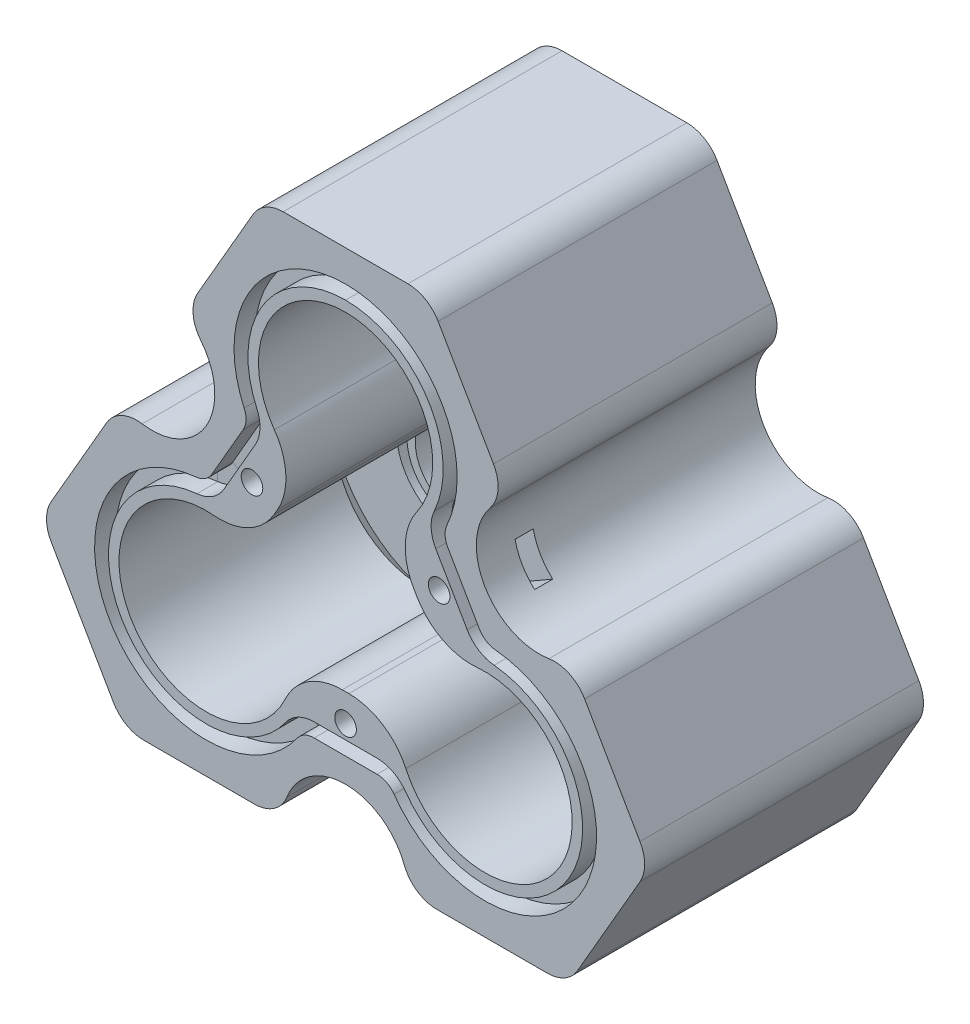
SolidWorks part; units mm, degrees
ref_plane "前视基准面" through (0, 0, 0) normal (0, 0, 1) x (1, 0, 0)
ref_plane "上视基准面" through (0, 0, 0) normal (0, 1, 0) x (1, 0, 0)
ref_plane "右视基准面" through (0, 0, 0) normal (1, 0, 0) x (0, 0, -1)
ref_plane "基准面1" through (0, -12.4, 0) normal (0, 1, 0) x (1, 0, 0)
sketch "草图2" plane through (0, 0, 0) normal (0, 0, 1) x (1, 0, 0)
  line L1 (-9.7628, 6.1843) -> (-10.2372, 5.3627)
  line L2 (-0.4744, -11.547) -> (0.4744, -11.547)
  line L3 (10.2372, 5.3627) -> (9.7628, 6.1843)
  circle A0 centre (0, 0) radius 11.547 construction
  arc A1 (10.2076, 15.8791) -> (-10.2076, 15.8791) centre (0, 23.094) ccw
  circle A2 centre (0, 23.094) radius 7.5
  arc A3 (8.6479, -16.7796) -> (18.8555, 0.9005) centre (20, -11.547) ccw
  circle A4 centre (20, -11.547) radius 7.5
  arc A5 (-18.8555, 0.9005) -> (-8.6479, -16.7796) centre (-20, -11.547) ccw
  circle A6 centre (-20, -11.547) radius 7.5
  arc A7 (9.7628, 6.1843) -> (10.2076, 15.8791) centre (17.557, 10.6843) cw
  arc A8 (10.2372, 5.3627) -> (18.8555, 0.9005) centre (18.0314, 9.8627) ccw
  arc A9 (8.6479, -16.7796) -> (0.4744, -11.547) centre (0.4744, -20.547) ccw
  arc A10 (-0.4744, -11.547) -> (-8.6479, -16.7796) centre (-0.4744, -20.547) ccw
  arc A11 (-9.7628, 6.1843) -> (-10.2076, 15.8791) centre (-17.557, 10.6843) ccw
  arc A12 (-10.2372, 5.3627) -> (-18.8555, 0.9005) centre (-18.0314, 9.8627) cw
  circle A13 centre (0, 0) radius 6
  circle A14 centre (0, 23.094) radius 12.5
  circle A15 centre (20, -11.547) radius 12.5
  circle A16 centre (-20, -11.547) radius 12.5
  dimension "D2" = 25
  dimension "D3" = 15
  dimension "D1" = 9
  dimension "D5" = 12
  dimension "D4" = 3
  dimension "D6" = 3
sketch "草图3" plane through (0, 0, 0) normal (0, 0, 1) x (1, 0, 0)
  line L0 (0, 0) -> (0, -32.047) construction
  line L1 (0, 64.094) -> (-55.507, -32.047)
  line L2 (-55.507, -32.047) -> (55.507, -32.047)
  line L3 (55.507, -32.047) -> (0, 64.094)
  line L4 (0, -87.188) -> (75.507, 43.594)
  line L5 (75.507, 43.594) -> (-75.507, 43.594)
  line L6 (-75.507, 43.594) -> (0, -87.188)
  circle A0 centre (0, 0) radius 32.047 construction
  circle A1 centre (0, 0) radius 43.594 construction
  arc A9 (10.2076, 15.8791) -> (-10.2076, 15.8791) centre (0, 23.094) ccw construction
  arc A10 (-18.8555, 0.9005) -> (-8.6479, -16.7796) centre (-20, -11.547) ccw construction
  circle A11 centre (-27.7535, 16.0235) radius 9
  circle A12 centre (27.7535, 16.0235) radius 9
  circle A13 centre (0, -32.047) radius 9
  dimension "D1" = 8
  dimension "D2" = 8
  dimension "D3" = 18
  dimension "D4" = 3
extrude "凸台-拉伸1" add sketch "草图3" along normal blind 36 contours L1 L6 L2 L4 L3 L5 region at (0, 0, 0)
extrude "切除-拉伸1" cut sketch "草图2" along normal blind 32 from offset 4 contours A16 A10 L2 A9 A15 A8 L3 A7 A14 A11 L1 A12 A13 | A13 region at (-8.0682, 11.1196, 0) region at (0, 0, 0)
extrude "切除-拉伸2" cut sketch "草图2<3>" along normal blind 32 from offset 4 contours A1 A14 A2 | A2 | A5 A16 A6 | A6 | A3 A15 A4 | A4 region at (-3.6781, 34.6702, 0) region at (-11.0266, -3.3608, 0) region at (28.1862, -2.5736, 0) region at (0, 23.094, 0) region at (20, -11.547, 0) region at (-20, -11.547, 0)
sketch "草图2<3>" plane through (0, 0, 0) normal (0, 0, 1) x (1, 0, 0) same geometry as "草图2"
sketch "草图4" plane through (0, 0, 0) normal (1, 0, 0) x (0, 0, -1)
  line L0 (0, 23.094) -> (-36, 23.094) construction
  line L1 (-36, 23.8177) -> (-36, 43.594) construction
  line L2 (0, 23.094) -> (0, 41.594)
  line L3 (0, 23.094) -> (-5, 23.094)
  line L4 (-5, 23.094) -> (-5, 35.594)
  line L5 (0, 23.8177) -> (0, 43.594) construction
  arc A0 (-5, 35.594) -> (0, 41.594) centre (8.626, 29.3224) cw
  dimension "D4" = 15
  dimension "D1" = 5
  dimension "D2" = 12.5
  dimension "D3" = 18.5
revolve "切除-旋转1" cut sketch "草图4" angle 360 about L0 region at (0, 31.2032, 2.3495)
sketch "草图5" plane through (0, 0, 0) normal (1, 0, 0) x (0, 0, -1)
  line L0 (0, 0) -> (-36, 0) construction
  line L1 (-36, -11.547) -> (-36, 8.2293) construction
pattern_circular "阵列(圆周)1" count 3 over 360 about axis through (0, 0, 0) along (0, 0, 1) of "切除-旋转1"
extrude "凸台-拉伸2" add sketch "草图3<3>" against normal blind 4 contours A13 L2 L4 L3 A12 L5 L1 A11 L6 region at (0, 0, 0)
sketch "草图3<3>" plane through (0, 0, 0) normal (0, 0, 1) x (1, 0, 0) same geometry as "草图3"
fillet "圆角1" radius 5 12 edges at (32.2535, 8.2293, 16) (43.6714, -11.547, 16) (31.8357, -32.047, 16) (9, -32.047, 16) (-9, -32.047, 16) (-31.8357, -32.047, 16) (-43.6714, -11.547, 16) (-32.2535, 8.2293, 16) (-23.2535, 23.8177, 16) (-11.8357, 43.594, 16) (11.8357, 43.594, 16) (23.2535, 23.8177, 16)
sketch "草图6" plane through (0, 0, 36) normal (0, 0, 1) x (1, 0, 0)
  line L0 (-13.8081, 13.1776) -> (-18.3162, 5.3694)
  line L1 (-4.5081, -18.547) -> (4.5081, -18.547)
  line L2 (18.3162, 5.3694) -> (13.8081, 13.1776)
  arc A0 (13.636, 16.8442) -> (-13.636, 16.8442) centre (0, 23.094) ccw
  arc A1 (7.7695, -20.2312) -> (21.4055, 3.387) centre (20, -11.547) ccw
  arc A2 (-21.4055, 3.387) -> (-7.7695, -20.2312) centre (-20, -11.547) ccw
  arc A3 (13.8081, 13.1776) -> (13.636, 16.8442) centre (17.2722, 15.1776) cw
  arc A4 (18.3162, 5.3694) -> (21.4055, 3.387) centre (21.7803, 7.3694) ccw
  arc A5 (7.7695, -20.2312) -> (4.5081, -18.547) centre (4.5081, -22.547) ccw
  arc A6 (-4.5081, -18.547) -> (-7.7695, -20.2312) centre (-4.5081, -22.547) ccw
  arc A7 (-21.4055, 3.387) -> (-18.3162, 5.3694) centre (-21.7803, 7.3694) ccw
  arc A8 (-13.8081, 13.1776) -> (-13.636, 16.8442) centre (-17.2722, 15.1776) ccw
  dimension "D1" = 30
  dimension "D4" = 4
  dimension "D3" = 3
  dimension "D2" = 3
sketch "草图7" plane through (0, 0, 0) normal (-1, 0, 0) x (0, 1, 0)
  line L1 (39.094, -39) -> (37.094, -39)
  line L2 (39.094, -39) -> (39.094, -33)
  line L3 (39.094, -33) -> (37.094, -33)
  line L4 (37.094, -39) -> (37.094, -33)
  line L5 (39.094, -39) -> (37.094, -33) construction
  line L6 (39.094, -33) -> (37.094, -39) construction
  point P0 (38.094, -36)
  dimension "D1" = 2
  dimension "D2" = 6
sweep "切除-扫描1" cut profiles "草图7" path "草图6"
sketch "草图8" plane through (0, 0, 36) normal (0, 0, 1) x (1, 0, 0)
  line L0 (0, 0) -> (-10, 5.7735) construction
  line L1 (-9.7628, 6.1843) -> (-10.2372, 5.3627) construction
  line L2 (-10, 5.7735) -> (-19.9593, 11.5235) construction
  arc A0 (-29.1731, 7.1362) -> (-20.7666, 21.6966) centre (-27.7535, 16.0235) ccw construction
  circle A4 centre (-13.4234, 7.75) radius 1.55
  circle A5 centre (13.4234, 7.75) radius 1.55
  circle A6 centre (0, -15.5) radius 1.55
  dimension "D1" = 3.1
  dimension "D2" = 15.5
  dimension "D3" = 3
extrude "切除-拉伸4" cut sketch "草图8" against normal blind 8
sketch "草图11" plane through (0, -12.4, 0) normal (0, 1, 0) x (1, 0, 0)
  line L0 (-1.3566, -28) -> (1.1242, -28) construction
  line L1 (-8.4064, -36) -> (8.4064, -36) construction
  line L3 (-2.8, -30.6302) -> (2.8, -30.6302)
  line L4 (-2.8, -30.6302) -> (-2.8, -28.0302)
  line L5 (-2.8, -28.0302) -> (2.8, -28.0302)
  line L6 (2.8, -30.6302) -> (2.8, -28.0302)
  line L7 (-2.8, -30.6302) -> (2.8, -28.0302) construction
  line L8 (-2.8, -28.0302) -> (2.8, -30.6302) construction
  line L9 (0, 0) -> (0, -29.3302) construction
  point P4 (0, -29.3302)
  dimension "D1" = 8
  dimension "D3" = 2.8
  dimension "D4" = 2.6
extrude "切除-拉伸5" cut sketch "草图11" against normal through all from offset 1 offset against normal yes
sketch "草图12" plane through (0, 0, 4) normal (0, 0, 1) x (1, 0, 0)
  circle A0 centre (0, 0) radius 5
  dimension "D1" = 10
extrude "切除-拉伸7" cut sketch "草图12" against normal blind 1.5
sketch "草图13" plane through (0, 0, 0) normal (0, 0, 1) x (1, 0, 0)
  circle A0 centre (-20, -11.547) radius 6
  dimension "D1" = 12
extrude "切除-拉伸8" cut sketch "草图13" against normal blind 3
pattern_circular "阵列(圆周)3" count 3 over 360 about axis through (0, 0, 2.5) along (0, 0, 1) of "切除-拉伸8"
sketch "草图14" plane through (0, 0, 0) normal (0, 0, 1) x (1, 0, 0)
  circle A0 centre (-20, -11.547) radius 7.2
  circle A1 centre (-20, -11.547) radius 8.7
  dimension "D1" = 1.5
  dimension "D2" = 14.4
extrude "切除-拉伸9" cut sketch "草图14" against normal blind 2
pattern_circular "阵列(圆周)4" count 3 over 360 about axis through (0, 0, 2.5) along (0, 0, 1) of "切除-拉伸9"
pattern_circular "阵列(圆周)5" count 3 over 360 about axis through (0, 0, 2.5) along (0, 0, 1) of "切除-拉伸5"
